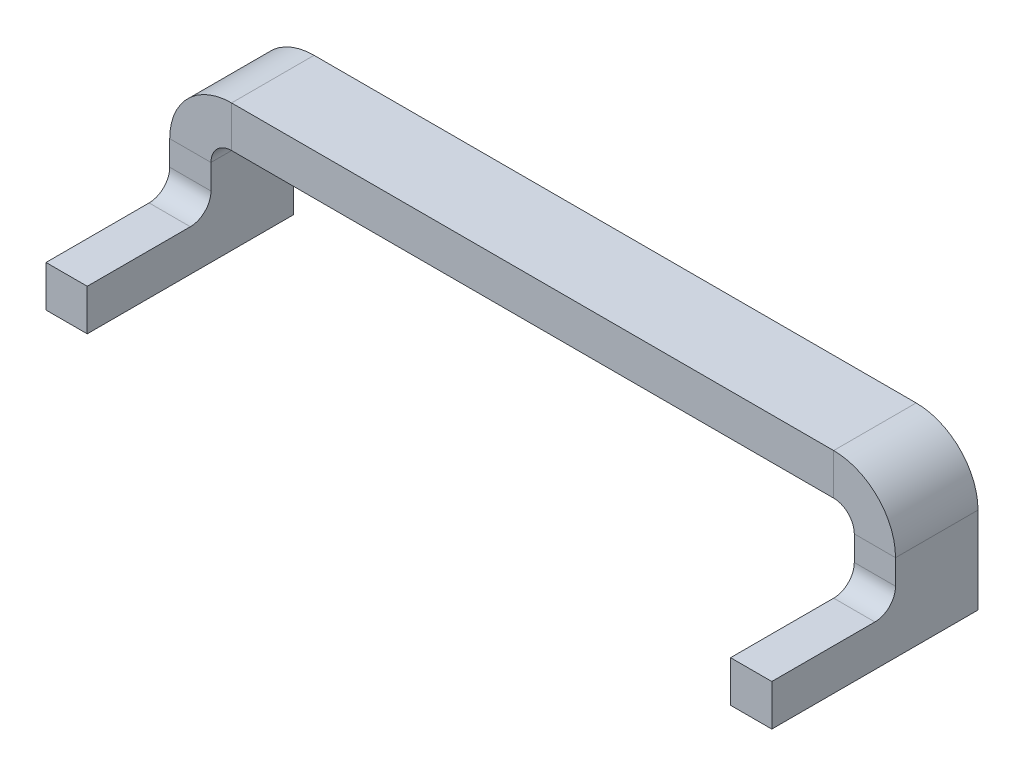
SolidWorks part; units mm, degrees
note: The reader was unsure of these and kept them because the rebuilt part matched: flange length of "Edge-Flange1".
ref_plane "Front Plane" through (0, 0, 0) normal (0, 0, 1) x (1, 0, 0)
ref_plane "Top Plane" through (0, 0, 0) normal (0, 1, 0) x (1, 0, 0)
ref_plane "Right Plane" through (0, 0, 0) normal (1, 0, 0) x (0, 0, -1)
sketch "Sketch2" plane through (0, 0, 0) normal (0, 1, 0) x (1, 0, 0)
  line L0 (78, 0) -> (-78, 0)
  line L4 (-78, -20) -> (78, -20)
  line L8 (-78, 0) -> (-78, -20)
  line L9 (78, 0) -> (78, -20)
  point P4 (0, 0)
  dimension "D1" = 156
  dimension "D2" = 20
base flange "Base-Flange1" sketch "Sketch2" thickness 10 reverse thickness direction yes parameters "D1"=2
edge flange "Edge-Flange1" sketch "Sketch11" flange profiles "Sketch11", "Sketch12" flange angle 90 flange length 36 flange position material outside bend radius 5 thickness 10 relief rectangular parameters "D6"=10, "D8"=1
sketch "Sketch11" plane through (-78, 0, 0) normal (1, 0, 0) x (0, 0, 1)
  line L2 (0, 0) -> (0, 26)
  line L3 (0, 26) -> (20, 26)
  line L4 (20, 26) -> (20, 0)
  line L5 (20, 0) -> (0, 0) construction
  line L6 (20, 0) -> (0, 0)
sketch "Sketch12" plane through (78, 0, 0) normal (-1, 0, 0) x (0, 0, -1)
  line L0 (0, 0) -> (-20, 0) construction
  line L1 (0, 0) -> (-20, 0)
  line L2 (0, 0) -> (0, 26)
  line L3 (0, 26) -> (-20, 26)
  line L4 (-20, 26) -> (-20, 0)
bend "EdgeBend1" bend radius 5 bend angle 90 parameters "D5"=1
bend "EdgeBend2" bend radius 5 bend angle 90 parameters "D5"=2
sketch "Sketch15" plane through (0, -26, 0) normal (0, -1, 0) x (1, 0, 0)
  line L0 (-88, 20) -> (-88, 0) construction
  line L1 (-78, 0) -> (-88, 0)
  line L2 (-78, 0) -> (-78, 50)
  line L3 (-78, 50) -> (-88, 50)
  line L4 (-88, 0) -> (-88, 50)
  line L5 (78, 0) -> (78, 20) construction
  line L6 (88, 0) -> (78, 0)
  line L7 (88, 0) -> (88, 50)
  line L8 (88, 50) -> (78, 50)
  line L9 (78, 0) -> (78, 50)
  dimension "D1" = 50
  dimension "D2" = 50
extrude "Boss-Extrude1" add sketch "Sketch15" against normal blind 10
fillet "Fillet3" radius 5 2 edges at (-83, -16, 20) (83, -16, 20)
sketch "Bend-Lines1" [suppressed] plane through (0, 0, 0) normal (0, 1, 0) x (1, 0, 0)
sketch "Bounding-Box1" [suppressed] plane through (0, 0, 0) normal (0, 1, 0) x (1, 0, 0)
sheet metal parameters "Sheet-Metal1" thickness 10 parameters "D1"=2
flat pattern "Flat-Pattern1" [suppressed]
sketch "Bend-Lines2" plane through (0, 0, 0) normal (0, 1, 0) x (1, 0, 0)
sketch3d "Bounding-Box2" [suppressed]
  line L0 (78, -19, 0) -> (-78, -19, 0) construction
  line L1 (78, 0, 0) -> (-78, 0, 0) construction
  line L2 (78, -19, 0) -> (78, 0, 0) construction
  line L3 (-78, -19, 0) -> (-78, 0, 0) construction
sheet metal parameters "Sheet-Metal2" thickness 10 parameters "D1"=2
flat pattern "Flat-Pattern1"
sketch "Bend-Lines2" plane through (0, 0, 0) normal (0, -1, 0) x (-1, 0, 0)
  line L0 (-81.4978, 0) -> (-81.4978, -19) construction
  line L1 (81.4978, -19) -> (81.4978, 0) construction
  line L2 (-81.4978, 0) -> (-81.4978, -19) construction
  line L3 (81.4978, -19) -> (81.4978, 0) construction
sketch3d "Bounding-Box2" [suppressed]
  line L0 (-100.9956, -19, 0) -> (100.9956, -19, 0) construction
  line L1 (-100.9956, 0, 0) -> (100.9956, 0, 0) construction
  line L2 (-100.9956, -19, 0) -> (-100.9956, 0, 0) construction
  line L3 (100.9956, -19, 0) -> (100.9956, 0, 0) construction
bend of the flat pattern "Flatten-<EdgeBend1>1"
bend of the flat pattern "Flatten-<EdgeBend2>1"
sheet metal parameters "Sheet-Metal3" thickness 10 parameters "D1"=2
flat pattern "Flat-Pattern1"
sketch "Bend-Lines2" plane through (0, 0, 0) normal (0, -1, 0) x (-1, 0, 0)
  line L0 (-80.854, 0) -> (-80.854, -20) construction
  line L1 (80.854, -20) -> (80.854, 0) construction
  line L2 (-80.854, 0) -> (-80.854, -20) construction
  line L3 (80.854, -20) -> (80.854, 0) construction
sketch3d "Bounding-Box2" [suppressed]
  line L0 (-109.708, -50, 0) -> (109.708, -50, 0) construction
  line L1 (-109.708, 0, 0) -> (109.708, 0, 0) construction
  line L2 (-109.708, -50, 0) -> (-109.708, 0, 0) construction
  line L3 (109.708, -50, 0) -> (109.708, 0, 0) construction
bend of the flat pattern "Flatten-<EdgeBend1>1"
bend of the flat pattern "Flatten-<EdgeBend2>1"
